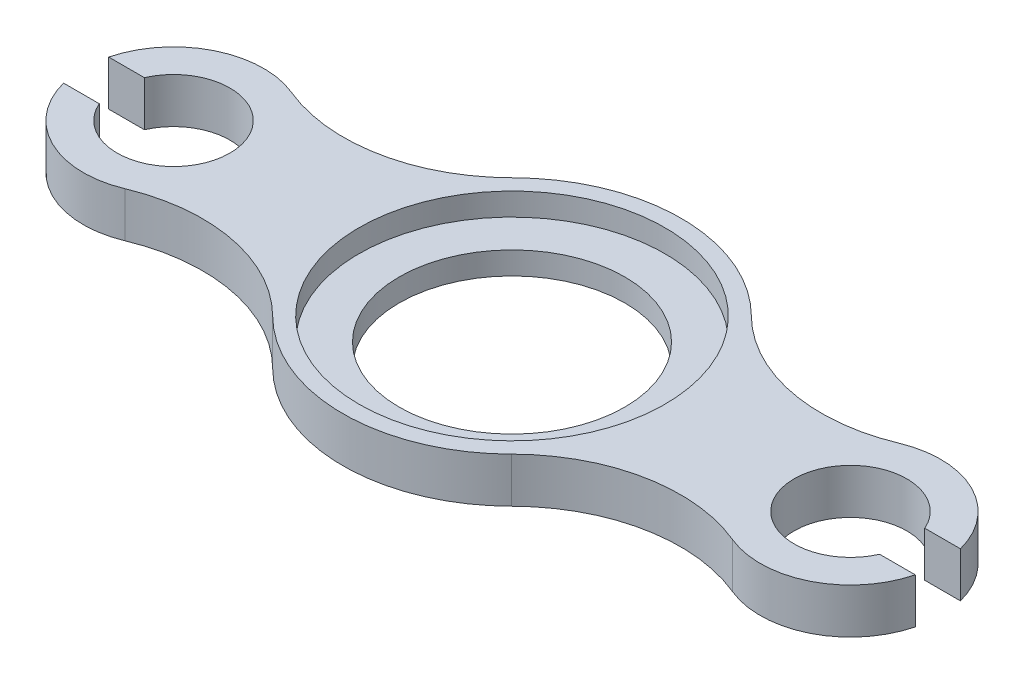
SolidWorks part; units mm, degrees
ref_plane "Front Plane" through (0, 0, 0) normal (0, 0, 1) x (1, 0, 0)
ref_plane "Top Plane" through (0, 0, 0) normal (0, 1, 0) x (1, 0, 0)
ref_plane "Right Plane" through (0, 0, 0) normal (1, 0, 0) x (0, 0, -1)
sketch "Sketch1" plane through (0, 0, 0) normal (0, 1, 0) x (1, 0, 0)
  line L0 (-170.098, 0) -> (170.098, 0) construction
  line L1 (-172.9129, 10) -> (-188.7298, 10)
  line L2 (188.7298, 10) -> (172.9129, 10)
  line L3 (188.7298, -10) -> (172.9129, -10)
  line L4 (-172.9129, -10) -> (-188.7298, -10)
  arc A0 (-188.7298, 10) -> (-134.6667, 36.9444) centre (-150, 0) cw
  arc A1 (-134.6667, 36.9444) -> (-52.9583, 53.1076) centre (-105.9167, 106.2152) ccw
  arc A2 (-52.9583, 53.1076) -> (52.9583, 53.1076) centre (0, 0) cw
  arc A3 (52.9583, 53.1076) -> (134.6667, 36.9444) centre (105.9167, 106.2152) ccw
  arc A4 (134.6667, 36.9444) -> (188.7298, 10) centre (150, 0) cw
  arc A5 (172.9129, 10) -> (172.9129, -10) centre (150, 0) ccw
  arc A6 (-172.9129, 10) -> (-172.9129, -10) centre (-150, 0) cw
  circle A7 centre (0, 0) radius 50
  circle A8 centre (0, 0) radius 67.8
  arc A9 (134.6667, -36.9444) -> (188.7298, -10) centre (150, 0) ccw
  arc A10 (52.9583, -53.1076) -> (134.6667, -36.9444) centre (105.9167, -106.2152) cw
  arc A11 (-52.9583, -53.1076) -> (52.9583, -53.1076) centre (0, 0) ccw
  arc A12 (-134.6667, -36.9444) -> (-52.9583, -53.1076) centre (-105.9167, -106.2152) cw
  arc A13 (-188.7298, -10) -> (-134.6667, -36.9444) centre (-150, 0) ccw
  point P4 (0, 0)
  point P24 (0, 0)
  point P25 (0, 0)
  point P26 (0, 0)
  point P27 (0, 0)
  dimension "D1" = 25
  dimension "D2" = 40
  dimension "D4" = 75
  dimension "D6" = 50
  dimension "D7" = 67.8
  dimension "D3" = 10
  dimension "D5" = 300
extrude "Boss-Extrude1" add sketch "Sketch1" along normal blind 20 contours A6 L0 A8 A5 L2 A4 A3 A2 A1 A0 L1 | L0 A6 L4 A13 A12 A11 A10 A9 L3 A5 A8 region at (0, 0, -71.6484) region at (96.4, 0, 3.8484)
extrude "Boss-Extrude2" add sketch "Sketch1<3>" along normal blind 10 contours A8 L0 A7 | L0 A8 A7 region at (0, 0, -51.5161) region at (58.9, 0, 1.5161)
sketch "Sketch1<3>" plane through (0, 0, 0) normal (0, 1, 0) x (1, 0, 0) same geometry as "Sketch1"
